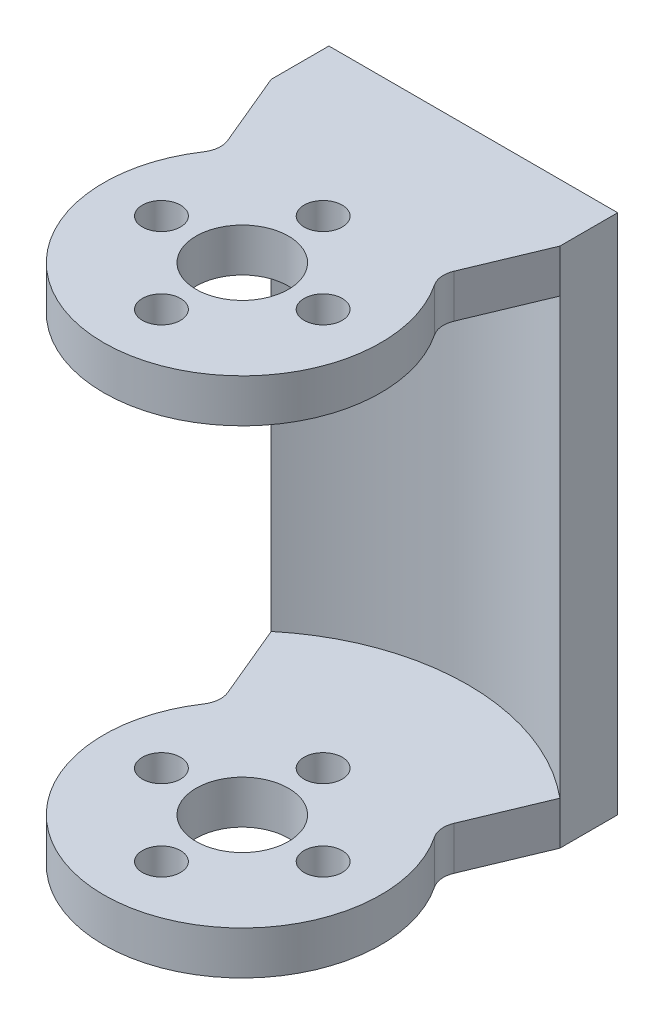
SolidWorks part; units mm, degrees
ref_plane "Front Plane" through (0, 0, 0) normal (0, 0, 1) x (1, 0, 0)
ref_plane "Top Plane" through (0, 0, 0) normal (0, 1, 0) x (1, 0, 0)
ref_plane "Right Plane" through (0, 0, 0) normal (1, 0, 0) x (0, 0, -1)
sketch "Sketch1" plane through (0, 0, 0) normal (0, 1, 0) x (1, 0, 0)
  line L2 (-12.5, 15) -> (-12.5, 20)
  line L3 (-12.5, 20) -> (12.5, 20)
  line L4 (12.5, 15) -> (12.5, 20)
  line L5 (-12.5, 15) -> (-9.3675, 7.5)
  line L6 (9.3675, 7.5) -> (12.5, 15)
  circle A3 centre (0, 0) radius 4
  arc A4 (-9.3675, 7.5) -> (9.3675, 7.5) centre (0, 0) ccw
  point P12 (-12.5, 0)
  point P13 (0, 20)
  dimension "D3" = 0
  dimension "D4" = 20
  dimension "D6" = 8
  dimension "D2" = 12
  dimension "D1" = 25
  dimension "D5" = 5
  dimension "D7" = 12.5
extrude "Boss-Extrude1" add sketch "Sketch1" along normal blind 45.15
sketch "Sketch2" plane through (-12.5, 0, 0) normal (-1, 0, 0) x (0, 0, 1)
  line L1 (25, 3.75) -> (-15, 3.75)
  line L2 (25, 3.75) -> (25, 41.4)
  line L3 (25, 41.4) -> (-15, 41.4)
  line L4 (-15, 3.75) -> (-15, 41.4)
  line L5 (-20, 45.15) -> (-20, 0) construction
  point P6 (-20, 22.575)
  point P7 (25, 22.575)
  dimension "D1" = 37.65
  dimension "D2" = 5
  dimension "D3" = 45
extrude "Cut-Extrude1" cut sketch "Sketch2" against normal through all
ref_plane "B mid plane" through (0, 22.575, 0) normal (0, -1, 0) x (-1, 0, 0)
sketch "Sketch3" plane through (0, 45.15, 0) normal (0, 1, 0) x (1, 0, 0)
  circle A0 centre (0, 7) radius 1.65
  circle A1 centre (0, 0) radius 4 construction
  dimension "D1" = 3.3
  dimension "D2" = 7
  dimension "D3" = 0
extrude "Cut-Extrude2" cut sketch "Sketch3" against normal through all
ref_axis "Axis1" through (0, 45.15, 0) along (0, -1, 0)
pattern_circular "CirPattern1" count 4 over 360 about axis through (0, 45.15, 0) along (0, -1, 0) of "Cut-Extrude2"
fillet "Fillet1" radius 2 4 edges at (9.3675, 43.275, -7.5) (9.3675, 1.875, -7.5) (-9.3675, 43.275, -7.5) (-9.3675, 1.875, -7.5)
sketch "Sketch4" plane through (0, 3.75, 0) normal (0, 1, 0) x (1, 0, 0)
  line L0 (9.8015, 8.5391) -> (12.5, 15) construction
  line L1 (-12.5, 15) -> (12.5, 15)
  arc A0 (-12.5, 15) -> (12.5, 15) centre (0, 0) cw
extrude "Cut-Extrude4" cut sketch "Sketch4" along normal up to surface (37.65 mm away) up to face at (7, 41.4, 1.65)
